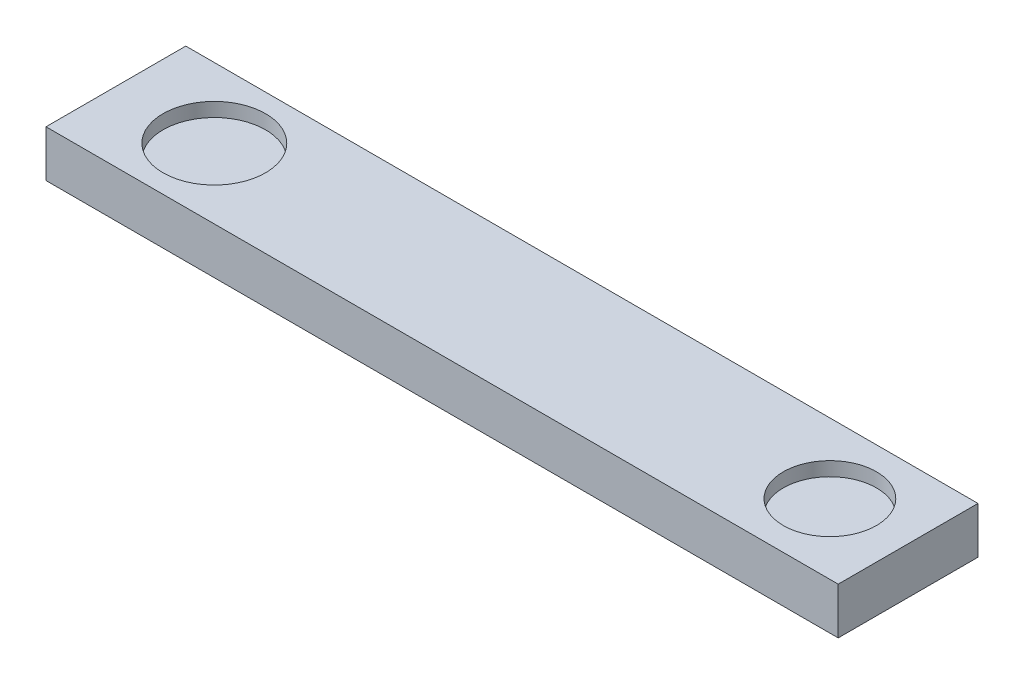
SolidWorks part; units mm, degrees
ref_plane "Front Plane" through (0, 0, 0) normal (0, 0, 1) x (1, 0, 0)
ref_plane "Top Plane" through (0, 0, 0) normal (0, 1, 0) x (1, 0, 0)
ref_plane "Right Plane" through (0, 0, 0) normal (1, 0, 0) x (0, 0, -1)
sketch "Sketch1" plane through (0, 0, 0) normal (0, 1, 0) x (1, 0, 0)
  line L1 (-85, -15) -> (85, -15)
  line L2 (-85, -15) -> (-85, 15)
  line L3 (-85, 15) -> (85, 15)
  line L4 (85, -15) -> (85, 15)
  line L5 (-85, -15) -> (85, 15) construction
  line L6 (-85, 15) -> (85, -15) construction
  point P0 (0, 0)
  dimension "D1" = 170
  dimension "D2" = 30
extrude "Boss-Extrude1" add sketch "Sketch1" along normal blind 10
sketch "Sketch2" plane through (0, 10, 0) normal (0, 1, 0) x (1, 0, 0)
  line L0 (-5.5, 0) -> (5.5, 0) construction
  circle A0 centre (68.2216, 0) radius 10
  circle A1 centre (-63.8815, 0) radius 11
  dimension "D1" = 20
  dimension "D2" = 22
extrude "Cut-Extrude1" cut sketch "Sketch2" against normal blind 3
